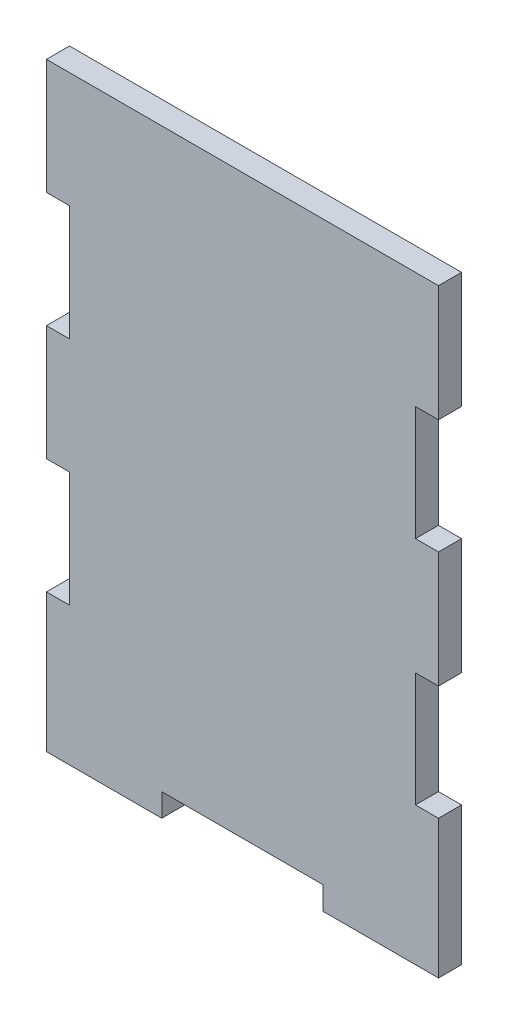
SolidWorks part; units mm, degrees
ref_plane "Front Plane" through (0, 0, 0) normal (0, 0, 1) x (1, 0, 0)
ref_plane "Top Plane" through (0, 0, 0) normal (0, 1, 0) x (1, 0, 0)
ref_plane "Right Plane" through (0, 0, 0) normal (1, 0, 0) x (0, 0, -1)
sketch "Sketch1" plane through (0, 0, 0) normal (0, 1, 0) x (1, 0, 0)
  line L1 (-50, -75) -> (50, -75)
  line L2 (-50, -75) -> (-50, 75)
  line L3 (-50, 75) -> (50, 75)
  line L4 (50, -75) -> (50, 75)
  line L5 (-50, -75) -> (50, 75) construction
  line L6 (-50, 75) -> (50, -75) construction
  point P0 (0, 0)
  dimension "D1" = 100
  dimension "D2" = 150
extrude "Boss-Extrude1" add sketch "Sketch1" along normal blind 150
sketch "Sketch13" plane through (50, 0, 0) normal (1, 0, 0) x (0, 0, -1)
  line L0 (-45, 40) -> (20, 0)
  line L1 (-75, 0) -> (-45, 0)
  line L2 (-75, 0) -> (-75, 40)
  line L3 (-75, 40) -> (-45, 40)
  line L5 (-75, 0) -> (75, 0) construction
  line L8 (-45, 0) -> (20, 0)
  dimension "D1" = 30
  dimension "D2" = 40
  dimension "D3" = 55
extrude "Cut-Extrude7" cut sketch "Sketch13" against normal up to next
shell "Shell1" thickness 5 removed face at (0, 150, 0)
sketch "Sketch3" plane through (0, 0, 0) normal (0, -1, 0) x (1, 0, 0)
  line L1 (50, 45) -> (50, 75) construction
  circle A0 centre (0, 60) radius 4
  circle A1 centre (-5, 50) radius 1.5
  circle A2 centre (5, 50) radius 1.5
  dimension "D3" = 8
  dimension "D4" = 3
  dimension "D5" = 10
  dimension "D7" = 10
  dimension "D8" = 5
  dimension "D1" = 60
  dimension "D2" = 50
extrude "Cut-Extrude2" cut sketch "Sketch3" against normal up to next
sketch "Sketch5" plane through (0, 0, 75) normal (0, 0, 1) x (1, 0, 0)
  line L0 (50, 150) -> (50, 40) construction
  line L1 (-25, 50) -> (25, 50)
  line L2 (-25, 50) -> (-25, 97)
  line L3 (-25, 97) -> (25, 97)
  line L4 (25, 50) -> (25, 97)
  line L5 (-25, 50) -> (25, 97) construction
  line L6 (-25, 97) -> (25, 50) construction
  line L7 (-50, 150) -> (50, 150) construction
  point P0 (0, 73.5)
  dimension "D1" = 50
  dimension "D2" = 47
  dimension "D3" = 50
  dimension "D4" = 76.5
extrude "Boss-Extrude3" add sketch "Sketch5" along normal blind 1
sketch "Sketch8" plane through (0, 0, 75) normal (0, 0, 1) x (1, 0, 0)
  line L0 (-50, 150) -> (-50, 40) construction
  line L1 (-25, 100) -> (25, 100)
  line L2 (-25, 100) -> (-25, 139)
  line L3 (-25, 139) -> (25, 139)
  line L4 (25, 100) -> (25, 139)
  line L5 (-25, 100) -> (25, 139) construction
  line L6 (-25, 139) -> (25, 100) construction
  line L7 (-50, 150) -> (50, 150) construction
  point P0 (0, 119.5)
  dimension "D1" = 50
  dimension "D2" = 39
  dimension "D3" = 50
  dimension "D4" = 50
extrude "Cut-Extrude3" cut sketch "Sketch8" against normal up to next
sketch "Sketch18" plane through (0, 0, 70) normal (0, 0, -1) x (-1, 0, 0)
  line L0 (-25, 139) -> (25, 139) construction
  line L1 (30, 99) -> (-26, 99)
  line L2 (30, 99) -> (30, 140)
  line L3 (30, 140) -> (-26, 140)
  line L4 (-26, 99) -> (-26, 140)
  line L6 (-25, 100) -> (-25, 139) construction
  line L7 (25, 139) -> (25, 100) construction
  dimension "D1" = 1
  dimension "D2" = 41
  dimension "D3" = 1
  dimension "D4" = 5
extrude "Cut-Extrude9" cut sketch "Sketch18" against normal blind 2
sketch "Sketch20" plane through (0, 0, 76) normal (0, 0, 1) x (1, 0, 0)
  line L0 (25, 97) -> (-25, 97) construction
  line L1 (-23, 96) -> (23, 96)
  line L2 (-23, 96) -> (-23, 51)
  line L3 (-23, 51) -> (23, 51)
  line L4 (23, 96) -> (23, 51)
  line L5 (-25, 50) -> (25, 50) construction
  line L6 (25, 50) -> (25, 97) construction
  line L7 (-25, 97) -> (-25, 50) construction
  dimension "D1" = 1
  dimension "D2" = 1
  dimension "D3" = 2
  dimension "D4" = 2
extrude "Cut-Extrude10" cut sketch "Sketch20" against normal blind 15 from offset 4 offset against normal yes
sketch "Sketch21" plane through (0, 45, 0) normal (0, 1, 0) x (1, 0, 0)
  line L1 (9, -52.5) -> (-9, -52.5)
  line L2 (9, -52.5) -> (9, -37.5)
  line L3 (9, -37.5) -> (-9, -37.5)
  line L4 (-9, -52.5) -> (-9, -37.5)
  circle A0 centre (5, -50) radius 1.5 construction
  circle A1 centre (-5, -50) radius 1.5 construction
  dimension "D3" = 4
  dimension "D1" = 4
  dimension "D2" = 2.5
  dimension "D4" = 15
extrude "Cut-Extrude11" cut sketch "Sketch21" against normal blind 2.5
sketch "Sketch22" plane through (-45, 0, 0) normal (1, 0, 0) x (0, 0, -1)
  line L0 (70, 150) -> (-70, 150) construction
  line L5 (70, 150) -> (70, 5) construction
  line L7 (-43.5848, 45) -> (21.4152, 5) construction
  line L8 (10, 150) -> (10, 12.0247)
  line L11 (10, 150) -> (5, 150)
  line L14 (5, 150) -> (5, 15.1017)
  line L15 (5, 15.1017) -> (10, 12.0247)
  dimension "D1" = 60
  dimension "D3" = 5
extrude "Boss-Extrude6" add sketch "Sketch22" along normal blind 5
mirror "Mirror2" about plane through (0, 0, 0) normal (1, 0, 0) of "Boss-Extrude6"
sketch "Sketch23" plane through (-45, 0, 0) normal (1, 0, 0) x (0, 0, -1)
  line L0 (16, 150) -> (21, 150)
  line L1 (70, 150) -> (10, 150) construction
  line L3 (21, 150) -> (21, 5.2555)
  line L4 (21, 5.2555) -> (16, 8.3324)
  line L6 (10, 12.0247) -> (10, 150) construction
  line L7 (16, 150) -> (16, 8.3324)
  line L8 (10, 12.0247) -> (21.4152, 5) construction
  dimension "D1" = 6
  dimension "D2" = 5
extrude "Boss-Extrude7" add sketch "Sketch23" along normal up to next
sketch "Sketch24" plane through (-45, 0, 0) normal (1, 0, 0) x (0, 0, -1)
  line L0 (70, 150) -> (70, 5) construction
  line L1 (70, 135) -> (67, 135)
  line L2 (70, 135) -> (70, 105)
  line L3 (70, 105) -> (67, 105)
  line L4 (67, 135) -> (67, 105)
  line L5 (70, 150) -> (21, 150) construction
  line L6 (70, 5) -> (21.4152, 5) construction
  line L7 (70, 20) -> (67, 20)
  line L8 (70, 20) -> (70, 50)
  line L9 (70, 50) -> (67, 50)
  line L10 (67, 20) -> (67, 50)
  dimension "D1" = 15
  dimension "D2" = 30
  dimension "D3" = 3
  dimension "D4" = 15
extrude "Cut-Extrude12" cut sketch "Sketch24" against normal through all both and the other way through all
sketch "Sketch28" plane through (0, 0, 76) normal (0, 0, 1) x (1, 0, 0)
  line L0 (-25, 73.5) -> (25, 73.5) construction
  line L1 (-25, 97) -> (-25, 50) construction
  line L2 (25, 50) -> (25, 97) construction
  line L3 (-25, 77.511) -> (25, 77.511) construction
  text T0 "SCAN\r\nHERE" font "Impact" height 10
extrude "Cut-Extrude14" cut sketch "Sketch28" against normal blind 1
sketch "Sketch30" plane through (0, 0, -75) normal (0, 0, -1) x (-1, 0, 0)
  text T0 "IBE VAN DE VEIRE\r\nSTEF GIELEN" font "Comic Sans MS" height 5
sketch "Sketch32" plane through (0, 150, 0) normal (0, 1, 0) x (1, 0, 0)
  line L0 (-50, 75) -> (-50, -75) construction
  line L1 (50, 75) -> (-50, 75) construction
  line L2 (-50, -75) -> (50, -75) construction
  line L3 (50, -75) -> (50, 75) construction
  circle A0 centre (-47, 72) radius 1.225
  circle A1 centre (-47, -72) radius 1.225
  circle A2 centre (47, -72) radius 1.225
  circle A3 centre (47, 72) radius 1.225
  dimension "D1" = 2.45
  dimension "D2" = 3
  dimension "D3" = 3
  dimension "D4" = 2.45
  dimension "D5" = 3
  dimension "D6" = 3
  dimension "D7" = 2.45
  dimension "D8" = 3
  dimension "D9" = 3
  dimension "D10" = 2.45
  dimension "D11" = 3
  dimension "D12" = 3
extrude "Cut-Extrude17" cut sketch "Sketch32" against normal blind 20
sketch "Sketch33" plane through (0, 150, 0) normal (0, 1, 0) x (1, 0, 0)
  line L1 (-45, 5) -> (45, 5)
  line L2 (-45, 5) -> (-45, 21)
  line L3 (-45, 21) -> (45, 21)
  line L4 (45, 5) -> (45, 21)
extrude "Cut-Extrude18" cut sketch "Sketch33" against normal blind 40
sketch "Sketch34" plane through (0, 150, 0) normal (0, 1, 0) x (1, 0, 0)
  line L0 (50, 75) -> (-50, 75) construction
  line L1 (-45, 75) -> (50, 75)
  line L2 (-45, 75) -> (-45, -75)
  line L3 (-45, -75) -> (50, -75)
  line L4 (50, 75) -> (50, -75)
sketch "Sketch36" plane through (0, 150, 0) normal (0, 1, 0) x (1, 0, 0)
  line L1 (-50, 75) -> (-50, -75) construction
  line L2 (-50, 70) -> (-50, -121.4049)
  line L4 (50, -75) -> (50, 75) construction
  line L5 (50, 70) -> (50, -121.4049)
  line L6 (50, -121.4049) -> (-50, -121.4049)
  line L7 (-50, 70) -> (-50, 75)
  line L8 (-45, 70) -> (-45, 75)
  line L9 (50, 75) -> (-50, 75) construction
  line L10 (-45, 75) -> (-50, 75)
  line L11 (45, 70) -> (45, 75)
  line L12 (45, 75) -> (50, 75)
  line L13 (50, 75) -> (50, 70)
  line L14 (45, 70) -> (-45, 70)
extrude "Cut-Extrude20" cut sketch "Sketch36" against normal through all
sketch "Sketch37" plane through (0, 0, -75) normal (0, 0, -1) x (-1, 0, 0)
  line L1 (-45, 150) -> (45, 150)
  line L2 (-45, 150) -> (-45, 0)
  line L3 (-45, 0) -> (45, 0)
  line L4 (45, 150) -> (45, 0)
extrude "Boss-Extrude8" add sketch "Sketch37" along normal blind 1
sketch "Sketch38" plane through (0, 0, -76) normal (0, 0, -1) x (-1, 0, 0)
  text T0 "Ibe Van de Veire \r\nStef Gielen" font "Comic Sans MS" height 5
extrude "Cut-Extrude21" cut sketch "Sketch38" against normal blind 1
sketch "Sketch39" plane through (45, 0, 0) normal (1, 0, 0) x (0, 0, -1)
  line L0 (76, 150) -> (76, 0) construction
  line L1 (70, 150) -> (76, 150)
  line L2 (70, 150) -> (70, 119.7763)
  line L3 (70, 119.7763) -> (76, 119.7763)
  line L4 (76, 150) -> (76, 119.7763)
  line L5 (70, 119.7763) -> (76, 119.7763) construction
extrude "Boss-Extrude9" add sketch "Sketch39" along normal blind 6
pattern_linear "LPattern1" count 3 spacing 60 along (0, -1, 0) of "Boss-Extrude9"
ref_plane "Plane1" through (3, 0, 0) normal (1, 0, 0) x (0, 0, -1)
ref_plane "Plane2" through (3, 0, 0) normal (1, 0, 0) x (0, 0, -1)
sketch "Sketch40" plane through (-45, 0, 0) normal (-1, 0, 0) x (0, 0, 1)
  line L0 (-70, 150) -> (-70, 0) construction
  line L1 (-76, 150) -> (-70, 150)
  line L2 (-76, 150) -> (-76, 120)
  line L3 (-76, 120) -> (-70, 120)
  line L4 (-70, 150) -> (-70, 120)
  dimension "D1" = 30
extrude "Boss-Extrude10" add sketch "Sketch40" along normal blind 6
pattern_linear "LPattern2" count 3 spacing 60 along (0, -1, 0) of "Boss-Extrude10"
sketch "Sketch41" plane through (0, 0, 0) normal (0, -1, 0) x (1, 0, 0)
  line L0 (51, -70) -> (45, -70) construction
  line L1 (-21, -70) -> (-51, -70)
  line L2 (-21, -70) -> (-21, -76)
  line L3 (-21, -76) -> (-51, -76)
  line L4 (-51, -70) -> (-51, -76)
  line L5 (-21, -70) -> (-21, -76) construction
  line L7 (51, -76) -> (21.0162, -76)
  line L8 (51, -76) -> (51, -70)
  line L9 (51, -70) -> (21.0162, -70)
  line L10 (21.0162, -76) -> (21.0162, -70)
  point P14 (0, 0)
extrude "Boss-Extrude11" add sketch "Sketch41" along normal blind 6
